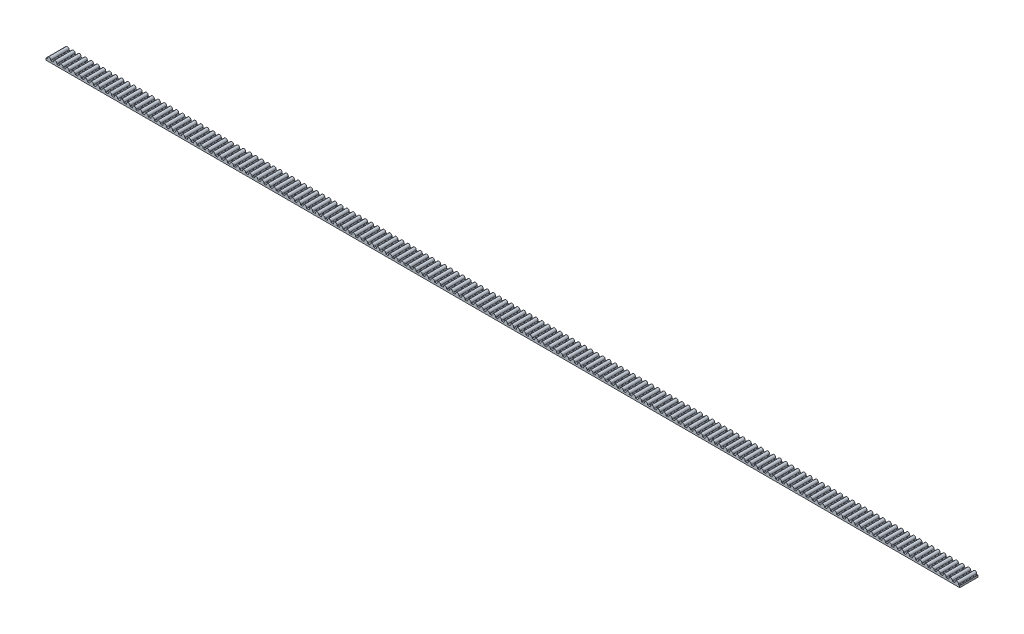
SolidWorks part; units mm, degrees
ref_plane "Front Plane" through (0, 0, 0) normal (0, 0, 1) x (1, 0, 0)
ref_plane "Top Plane" through (0, 0, 0) normal (0, 1, 0) x (1, 0, 0)
ref_plane "Right Plane" through (0, 0, 0) normal (1, 0, 0) x (0, 0, -1)
sketch "Sketch1" plane through (0, 0, 0) normal (0, 0, 1) x (1, 0, 0)
  line L0 (-150, 0) -> (150, 0) construction
  line L1 (-148.9976, 0) -> (-146.9976, 0) construction
  line L2 (-150, -0.695) -> (-150, -0.065) construction
  line L3 (-150, -0.065) -> (-149.7058, -0.065) construction
  line L4 (-148.9976, 0.695) -> (-148.9976, 0) construction
  line L5 (-148.9976, 0) -> (-148.9976, -0.695) construction
  line L6 (-148.2893, -0.065) -> (-147.9976, -0.065) construction
  line L7 (-148.9976, -0.695) -> (-147.9976, -0.695) construction
  line L8 (-147.9976, -0.695) -> (-146.9976, -0.695) construction
  arc A1 (-149.7058, -0.065) -> (-149.5562, 0.0956) centre (-149.7058, 0.085) ccw construction
  arc A2 (-148.439, 0.0956) -> (-148.2893, -0.065) centre (-148.2893, 0.085) ccw construction
  arc A4 (-149.5562, 0.0956) -> (-148.439, 0.0956) centre (-148.9976, 0.135) cw construction
  point P17 (-148.9976, -0.695)
  point P19 (-146.9976, -0.695)
  dimension "D4" = 0.15
  dimension "D6" = 0.56
  dimension "Length" = 300
  dimension "Pitch" = 2
  dimension "D2" = 0.63
  dimension "D1" = 0.2
  dimension "D7" = 0.2942
sketch "Sketch2" plane through (0, 0, 0) normal (1, 0, 0) x (0, 0, -1)
  line L0 (3, 0) -> (-3, 0) construction
  line L1 (3, -0.695) -> (3, 0.695) construction
  line L2 (-3, -0.695) -> (-3, 0.695) construction
  point P6 (3, 0)
  point P9 (-3, 0)
  dimension "Width" = 6
sketch "Sketch3" plane through (0, 0, 0) normal (0, 0, 1) x (1, 0, 0)
  line L1 (-150, -0.065) -> (150, -0.065)
  line L2 (-150, -0.065) -> (-150, -0.695)
  line L3 (-150, -0.695) -> (150, -0.695)
  line L4 (150, -0.065) -> (150, -0.695)
extrude "Boss-Extrude1" add sketch "Sketch3" along normal up to vertex (3 mm away) and the other way up to vertex (3 mm away) up to point (0, 0, 3) other way up to point (0, 0, -3)
sketch "Sketch4" plane through (0, 0, 0) normal (0, 0, 1) x (1, 0, 0)
  line L0 (-149.7058, -0.065) -> (-148.2893, -0.065)
  arc A1 (-148.439, 0.0956) -> (-148.2893, -0.065) centre (-148.2893, 0.085) ccw construction
  arc A2 (-149.7058, -0.065) -> (-149.5562, 0.0956) centre (-149.7058, 0.085) ccw construction
  arc A4 (-148.439, 0.0956) -> (-149.5562, 0.0956) centre (-148.9976, 0.135) ccw construction
  arc A6 (-148.439, 0.0956) -> (-148.2893, -0.065) centre (-148.2893, 0.085) ccw
  arc A7 (-149.7058, -0.065) -> (-149.5562, 0.0956) centre (-149.7058, 0.085) ccw
  arc A9 (-148.439, 0.0956) -> (-149.5562, 0.0956) centre (-148.9976, 0.135) ccw
extrude "Boss-Extrude2" add sketch "Sketch4" along normal up to vertex (3 mm away) and the other way up to vertex (3 mm away) up to point (0, 0, 3) other way up to point (0, 0, -3)
pattern_linear "LPattern1" count 150 spacing 2 along (1, 0, 0) of "Boss-Extrude2"
sketch "Sketch5" plane through (0, 0, 0) normal (0, 0, 1) x (1, 0, 0)
  line L0 (-150, -0.695) -> (-144, -0.695) construction
  line L1 (-150, -0.695) -> (150, -0.695) construction
  line L2 (150, -0.695) -> (144, -0.695) construction
  line L3 (-150, -0.38) -> (-144, -0.38) construction
  line L4 (-150, -0.065) -> (-150, -0.695) construction
  line L5 (150, -0.38) -> (144, -0.38) construction
  line L6 (150, -0.695) -> (150, -0.065) construction
  point P17 (144, -0.38)
  point P18 (144, -0.695)
  point P19 (-144, -0.38)
  point P20 (-144, -0.695)
  dimension "D1" = 6
  dimension "D2" = 6
equation "\"D3@LPattern1\"=\"Pitch@Sketch1\""
equation "\"D1@LPattern1\"=(\"Length@Sketch1\"/\"Pitch@Sketch1\")"
equation "\"D1@Sketch5\"=\"Pitch@Sketch1\"*3"
equation "\"D2@Sketch5\"=\"Width@Sketch2\""
